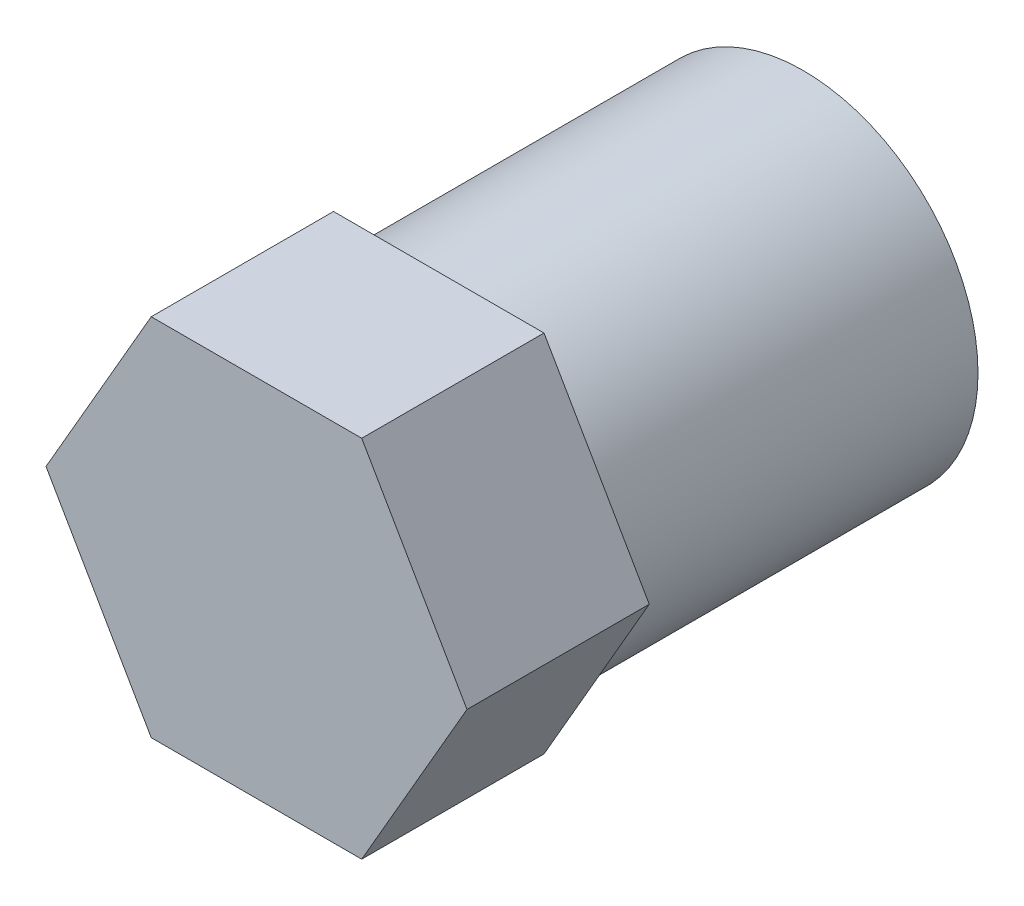
SolidWorks part; units mm, degrees
ref_plane "Front Plane" through (0, 0, 0) normal (0, 0, 1) x (1, 0, 0)
ref_plane "Top Plane" through (0, 0, 0) normal (0, 1, 0) x (1, 0, 0)
ref_plane "Right Plane" through (0, 0, 0) normal (1, 0, 0) x (0, 0, -1)
sketch "Sketch1" plane through (0, 0, 0) normal (0, 0, 1) x (1, 0, 0)
  line L0 (-3.4641, -6) -> (3.4641, -6)
  line L1 (3.4641, -6) -> (6.9282, 0)
  line L2 (6.9282, 0) -> (3.4641, 6)
  line L3 (3.4641, 6) -> (-3.4641, 6)
  line L4 (-3.4641, 6) -> (-6.9282, 0)
  line L5 (-6.9282, 0) -> (-3.4641, -6)
  circle A0 centre (0, 0) radius 3
  circle A1 centre (0, 0) radius 5.75
  point P8 (0, 0)
  point P10 (0, 6)
  dimension "D3" = 11.5
  dimension "D4" = 6
  dimension "D1" = 120
  dimension "D2" = 12
extrude "Boss-Extrude1" add sketch "Sketch1" along normal blind 6 contours L4 L5 L0 L1 L2 L3 A1 | A0 | A1 A0 region at (-5.0374, -2.9083, 0) region at (0, 0, 0) region at (-5.5874, 0, 0)
extrude "Boss-Extrude2" add sketch "Sketch1<3>" against normal blind 12 contours A1 A0 region at (-5.5874, 0, 0)
sketch "Sketch1<3>" plane through (0, 0, 0) normal (0, 0, 1) x (1, 0, 0) same geometry as "Sketch1"
ref_plane "Plane1" through (0, 0, 3) normal (0, 0, 1) x (1, 0, 0)
